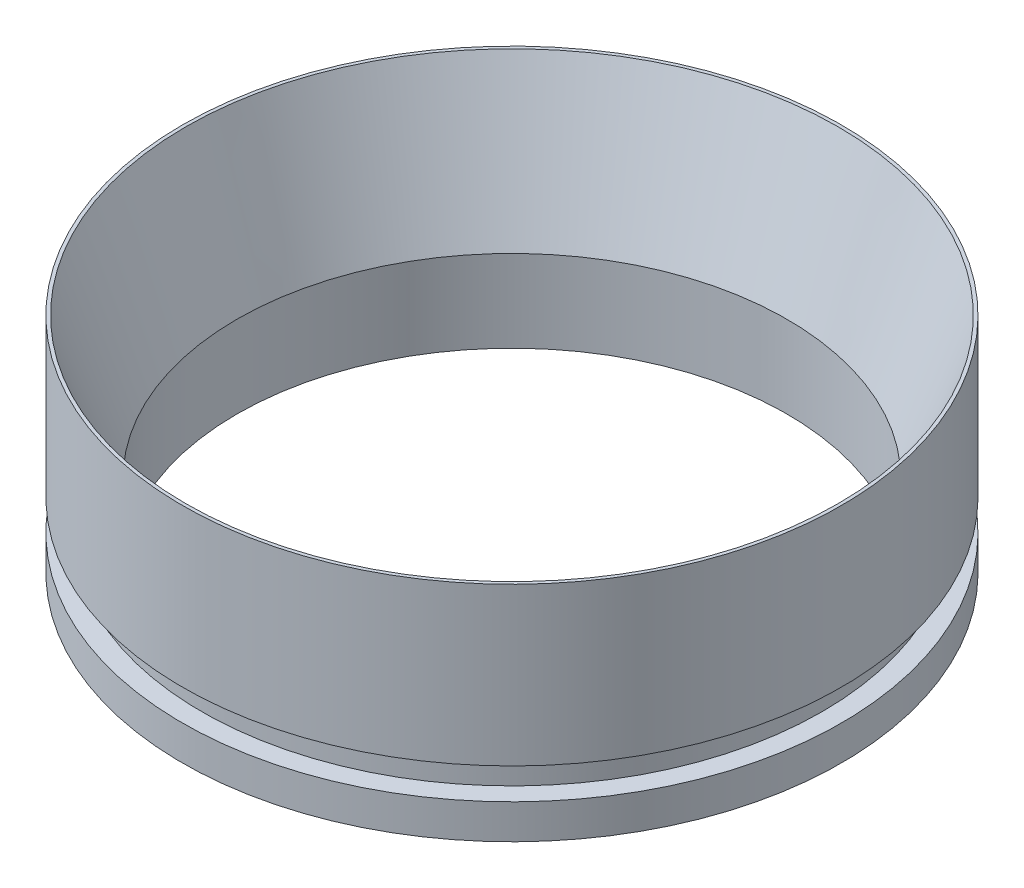
SolidWorks part; units mm, degrees
ref_plane "Front Plane" through (0, 0, 0) normal (0, 0, 1) x (1, 0, 0)
ref_plane "Top Plane" through (0, 0, 0) normal (0, 1, 0) x (1, 0, 0)
ref_plane "Right Plane" through (0, 0, 0) normal (1, 0, 0) x (0, 0, -1)
sketch "Sketch1" plane through (0, 0, 0) normal (0, 0, 1) x (1, 0, 0)
  line L0 (0, 0) -> (42.545, 0) construction
  line L3 (42.545, 12.7) -> (50.4825, 34.5081)
  line L4 (50.9905, 34.5081) -> (50.9905, 10.16)
  line L6 (50.9905, 0) -> (42.545, 0)
  line L7 (0, 35.9038) -> (0, 0) construction
  line L8 (0, 35.9038) -> (50.9905, 35.9038) construction
  line L9 (42.545, 12.7) -> (42.545, 35.9038) construction
  line L10 (50.4825, 34.5081) -> (50.9905, 34.5081)
  line L11 (50.4825, 34.5081) -> (50.9905, 35.9038) construction
  line L12 (50.9905, 35.9038) -> (50.9905, 34.5081) construction
  line L13 (42.545, 12.7) -> (42.545, 0)
  line L14 (50.9905, 10.16) -> (47.9806, 10.16)
  line L15 (47.9806, 10.16) -> (47.9806, 5.3594)
  line L16 (47.9806, 5.3594) -> (50.9905, 5.3594)
  line L17 (50.9905, 5.3594) -> (50.9905, 0)
  line L19 (42.545, 12.7) -> (42.545, 10.16) construction
  line L20 (42.545, 10.16) -> (47.9806, 10.16) construction
  dimension "D1" = 47.9806
  dimension "D2" = 42.545
  dimension "D3" = 20
  dimension "D4" = 50.9905
  dimension "D5" = 0.508
  dimension "D6" = 12.7
  dimension "D7" = 2.54
  dimension "D8" = 4.8006
revolve "Revolve1" add sketch "Sketch1" angle 360 about L7 region at (47.2782, 13.4366, 0)
